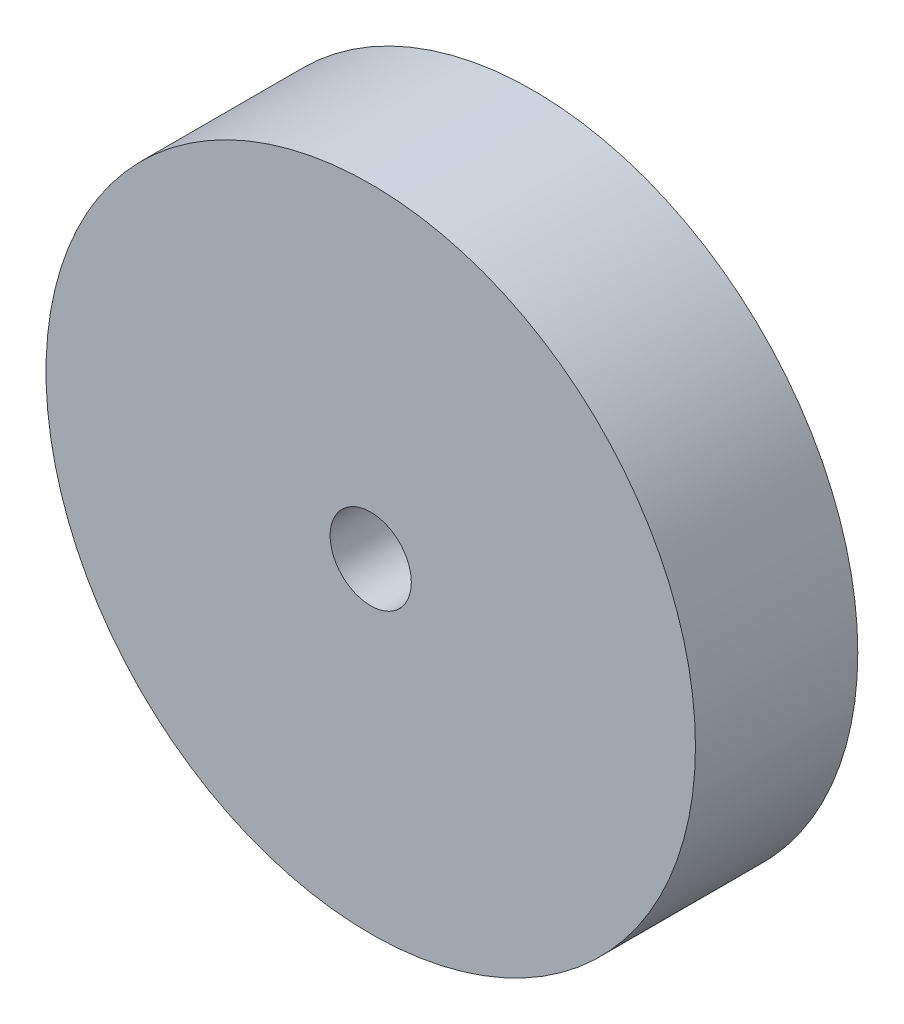
SolidWorks part; units mm, degrees
ref_plane "Front Plane" through (0, 0, 0) normal (1, 0, 0) x (0, 1, 0)
ref_plane "Top Plane" through (0, 0, 0) normal (0, 0, 1) x (0, 1, 0)
ref_plane "Right Plane" through (0, 0, 0) normal (0, 1, 0) x (-1, 0, 0)
sketch "Sketch3" plane through (0, 0, 0) normal (0, 0, 1) x (0, 1, 0)
  line L0 (0, 0) -> (25.4, 0) construction
  circle A0 centre (0, 0) radius 25.4
  circle A1 centre (0, 0) radius 3.175
  dimension "D1" = 50.8
  dimension "D2" = 6.35
extrude "base" add sketch "Sketch3" along normal blind 12.7
ref_plane "Plane1" through (-25.4, 0, 0) normal (-1, 0, 0) x (0, 0, 1)
sketch "Sketch5" plane through (-25.4, 0, 0) normal (-1, 0, 0) x (0, 0, 1)
  line L0 (0, 0) -> (12.7, 0) construction
  line L1 (12.7, -25.4) -> (12.7, 25.4) construction
  point P5 (6.35, 0)
sketch "Sketch6" plane through (0, 0, 0) normal (0, 0, -1) x (1, 0, 0)
  line L0 (0, 0) -> (8.4188, 0) construction
  line L1 (8.4188, 12.1803) -> (-6.8415, 12.1803)
  line L2 (8.4188, 12.1803) -> (8.4188, -12.1803)
  line L3 (8.4188, -12.1803) -> (-6.8415, -12.1803)
  line L4 (-6.8415, 12.1803) -> (-6.8415, -12.1803)
